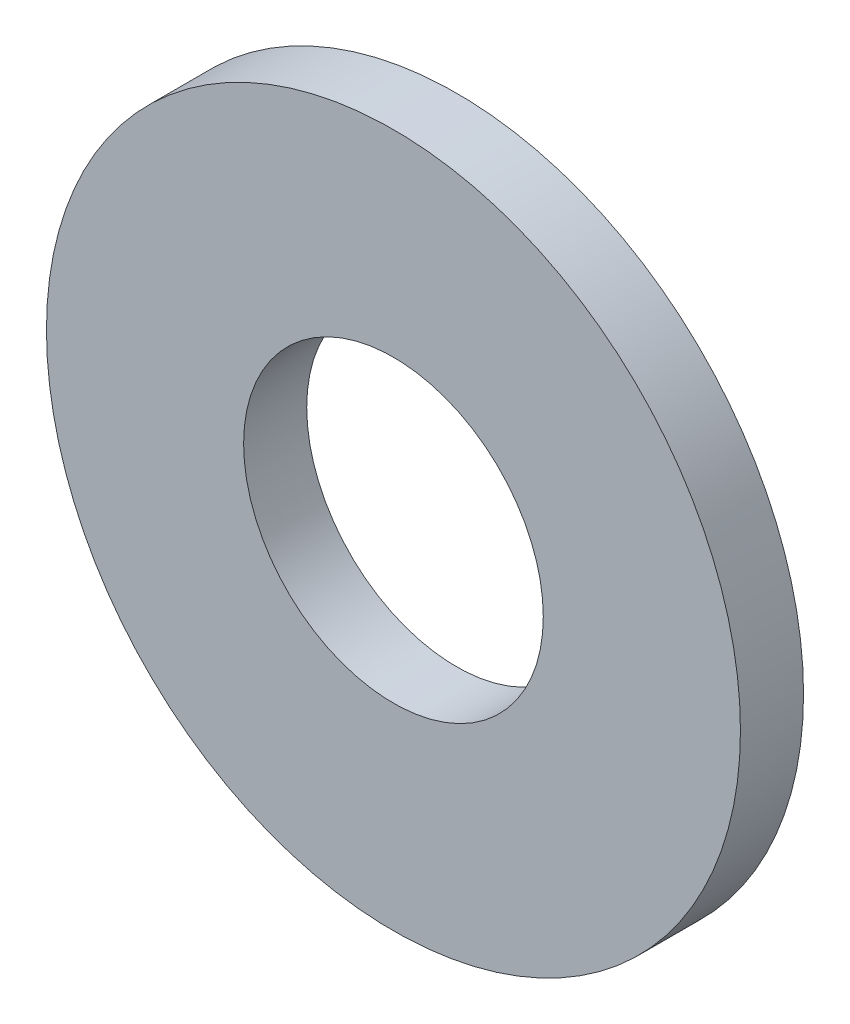
SolidWorks part; units mm, degrees
other "Imported1"
ref_plane "Front Plane" through (0, 0, 0) normal (0, 0, 1) x (1, 0, 0)
ref_plane "Top Plane" through (0, 0, 0) normal (0, 1, 0) x (1, 0, 0)
ref_plane "Right Plane" through (0, 0, 0) normal (1, 0, 0) x (0, 0, -1)
sketch "Sketch1" plane through (0, 0, 0) normal (0, 0, 1) x (1, 0, 0)
  line L0 (-5.588, 0) -> (5.588, 0) construction
  line L1 (-2.413, 0) -> (2.413, 0) construction
  circle A0 centre (0, 0) radius 2.413 construction
  circle A1 centre (0, 0) radius 5.588 construction
  point P8 (0, 0)
  point P9 (0, 5.588)
  point P11 (2.413, 0)
  dimension "ID" = 4.826
  dimension "OD" = 11.176
sketch "Sketch2" plane through (0, 0, 0) normal (1, 0, 0) x (0, 0, -1)
  line L0 (-0.508, 5.588) -> (0.508, 5.588) construction
  point P2 (0, 5.588)
  dimension "Thickness" = 1.016
sketch "Sketch3" plane through (0, 0, 0) normal (0, 0, 1) x (1, 0, 0)
  circle A0 centre (0, 0) radius 2.413
  circle A1 centre (0, 0) radius 5.588
extrude "Boss-Extrude1" add sketch "Sketch3" along normal up to vertex (0.508 mm away) and the other way up to vertex (0.508 mm away) up to point (0, 5.588, 0.508) other way up to point (0, 5.588, -0.508)
ref_axis "Center Axis 1" through (0, 0, 0.508) along (0, 0, -1)
